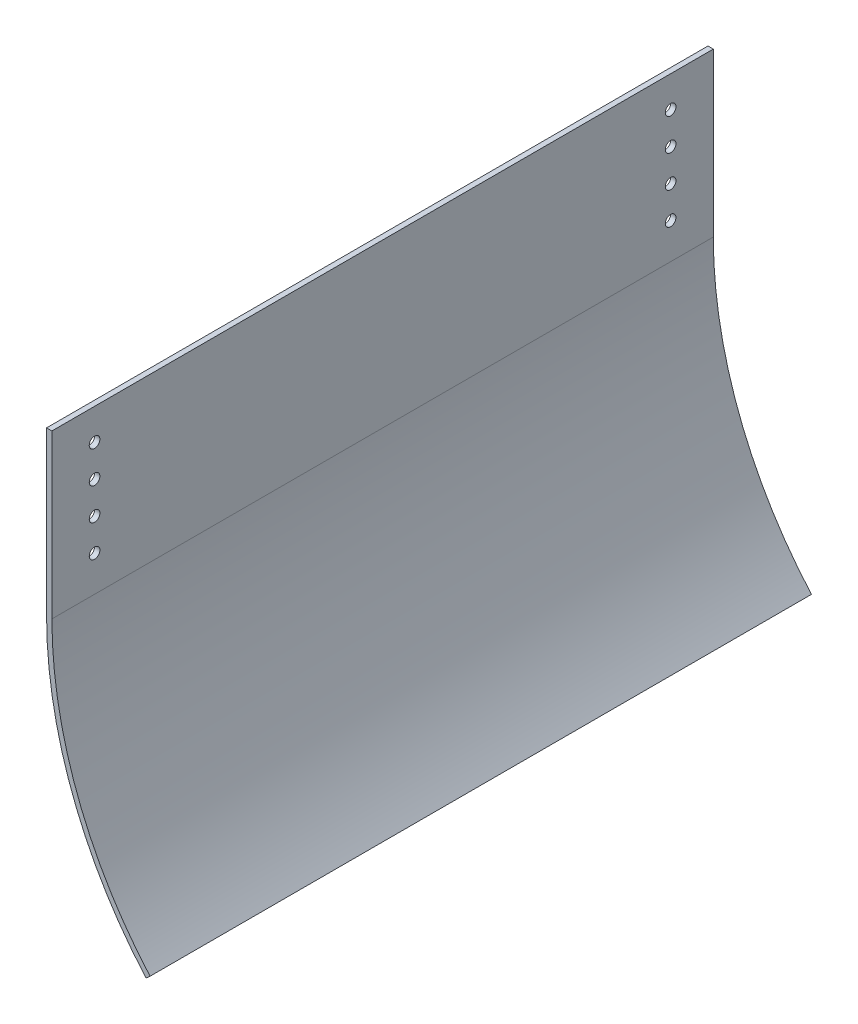
SolidWorks part; units mm, degrees
ref_plane "Front Plane" through (0, 0, 0) normal (0, 0, 1) x (1, 0, 0)
ref_plane "Top Plane" through (0, 0, 0) normal (0, 1, 0) x (1, 0, 0)
ref_plane "Right Plane" through (0, 0, 0) normal (1, 0, 0) x (0, 0, -1)
sketch "Sketch1" plane through (0, 0, 0) normal (0, 0, 1) x (1, 0, 0)
  line L2 (812.5417, 1387.3698) -> (812.5417, 1484.2708)
  line L4 (815.7167, 1387.3698) -> (815.7167, 1484.2708)
  line L5 (812.5417, 1484.2708) -> (815.7167, 1484.2708)
  line L6 (874.1429, 1232.3666) -> (871.7578, 1230.2708)
  arc A0 (812.5417, 1387.3698) -> (871.7578, 1230.2708) centre (1050.5397, 1387.3698) ccw
  arc A1 (815.7167, 1387.3698) -> (874.1429, 1232.3666) centre (1050.5397, 1387.3698) ccw
  dimension "D1" = 237.998
  dimension "D3" = 237.998
  dimension "D4" = 3.175
extrude "Boss-Extrude1" add sketch "Sketch1" along normal blind 393.7
sketch "Sketch2" plane through (815.7167, 0, 0) normal (1, 0, 0) x (0, 0, -1)
  line L1 (-393.7, 1387.3698) -> (-393.7, 1484.2708) construction
  line L2 (-393.7, 1484.2708) -> (0, 1484.2708) construction
  line L4 (0, 1387.3698) -> (0, 1484.2708) construction
  circle A0 centre (-368.3, 1446.6788) radius 3.175
  circle A1 centre (-368.3, 1427.6288) radius 3.175
  circle A2 centre (-368.3, 1408.5788) radius 3.175
  circle A3 centre (-25.4, 1465.7288) radius 3.175
  circle A4 centre (-25.4, 1446.6788) radius 3.175
  circle A5 centre (-25.4, 1427.6288) radius 3.175
  circle A6 centre (-368.3, 1465.7288) radius 3.175
  circle A7 centre (-25.4, 1408.5788) radius 3.175
  dimension "D1" = 6.35
  dimension "D2" = 6.35
  dimension "D3" = 6.35
  dimension "D11" = 6.35
  dimension "D13" = 6.35
  dimension "D14" = 6.35
  dimension "D15" = 6.35
  dimension "D16" = 6.35
  dimension "D4" = 18.542
  dimension "D5" = 19.05
  dimension "D6" = 19.05
  dimension "D7" = 25.4
  dimension "D8" = 25.4
  dimension "D9" = 25.4
  dimension "D10" = 25.4
  dimension "D12" = 19.05
  dimension "D17" = 25.4
  dimension "D18" = 25.4
  dimension "D19" = 25.4
  dimension "D20" = 25.4
  dimension "D21" = 18.542
  dimension "D22" = 19.05
  dimension "D23" = 19.05
  dimension "D24" = 19.05
extrude "Cut-Extrude1" cut sketch "Sketch2" against normal through all
